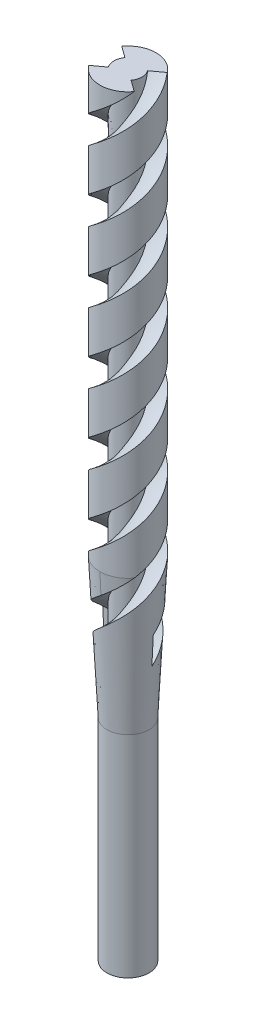
SolidWorks part; units mm, degrees
material "AISI Type 316L stainless steel"
ref_plane "Front Plane" through (0, 0, 0) normal (0, 0, 1) x (1, 0, 0)
ref_plane "Top Plane" through (0, 0, 0) normal (0, 1, 0) x (1, 0, 0)
ref_plane "Right Plane" through (0, 0, 0) normal (1, 0, 0) x (0, 0, -1)
sketch "Sketch1" plane through (0, 0, 0) normal (0, 0, 1) x (1, 0, 0)
  line L0 (0, 0) -> (0, -50000) construction
  line L1 (0, 332.4995) -> (4, 332.4995)
  line L2 (4, 332.4995) -> (4, 272.4995)
  line L3 (4, 272.4995) -> (3, 252.4995)
  line L4 (3, 252.4995) -> (3, 222.4995)
  line L5 (3, 222.4995) -> (0, 222.4995)
  line L6 (0, 222.4995) -> (0, 332.4995)
  dimension "D1" = 4
  dimension "D2" = 60
  dimension "D3" = 20
  dimension "D4" = 30
  dimension "D5" = 3
revolve "Revolve1" add sketch "Sketch1" angle 360 about L0
sketch "Sketch3" plane through (0, 332.4995, 0) normal (0, 1, 0) x (1, 0, 0)
  circle A1 centre (0, 0) radius 4
  circle A2 centre (0, 0) radius 4
  dimension "D1" = 0
curve "Helix/Spiral1" pitch 20 height 60 turns 3
sketch "Sketch4" plane through (0, 0, 0) normal (0, 0, 1) x (1, 0, 0)
  line L1 (-2, 334.4995) -> (-6, 334.4995)
  line L2 (-2, 334.4995) -> (-2, 330.4995)
  line L3 (-2, 330.4995) -> (-6, 330.4995)
  line L4 (-6, 334.4995) -> (-6, 330.4995)
  line L5 (-4, 330.4995) -> (-4, 334.4995) construction
  line L6 (-2, 332.4995) -> (-6, 332.4995) construction
  point P0 (-4, 332.4995)
  dimension "D1" = 4
sweep "Cut-Sweep1" cut profiles "Sketch4" path "Helix/Spiral1"
sketch "Sketch5" plane through (0, 332.4995, 0) normal (0, 1, 0) x (1, 0, 0)
  circle A0 centre (0, 0) radius 4
curve "Helix/Spiral2" pitch 20 height 60 turns 3
sketch "Sketch6" plane through (0, 0, 0) normal (0, 0, 1) x (1, 0, 0)
  line L1 (2, 334.4995) -> (6, 334.4995)
  line L2 (2, 334.4995) -> (2, 330.4995)
  line L3 (2, 330.4995) -> (6, 330.4995)
  line L4 (6, 334.4995) -> (6, 330.4995)
  line L5 (4, 330.4995) -> (4, 334.4995) construction
  line L6 (2, 332.4995) -> (6, 332.4995) construction
  point P0 (4, 332.4995)
  dimension "D1" = 4
sweep "Cut-Sweep2" cut profiles "Sketch6" path "Helix/Spiral2"
